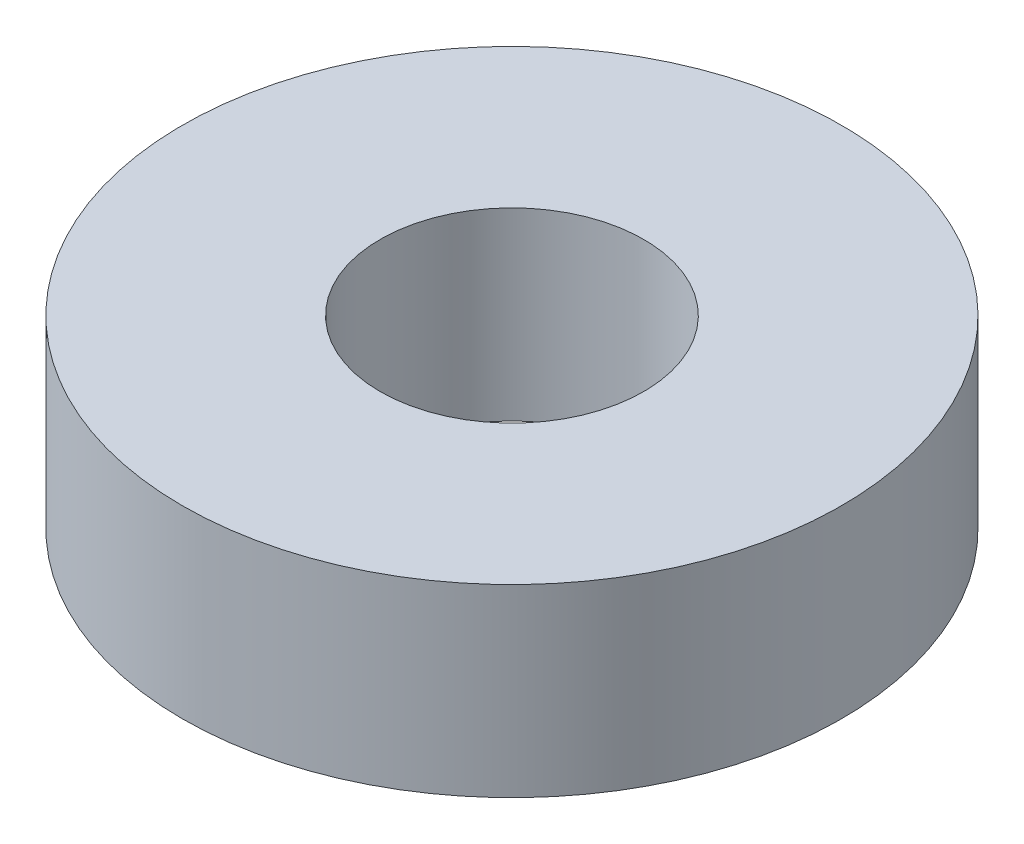
SolidWorks part; units mm, degrees
ref_plane "Front Plane" through (0, 0, 0) normal (0, 0, 1) x (1, 0, 0)
ref_plane "Top Plane" through (0, 0, 0) normal (0, 1, 0) x (1, 0, 0)
ref_plane "Right Plane" through (0, 0, 0) normal (1, 0, 0) x (0, 0, -1)
sketch "Sketch1" plane through (0, 0, 0) normal (0, 1, 0) x (1, 0, 0)
  circle A0 centre (0, 0) radius 50
  dimension "FLANGE_OD" = 100
extrude "Boss-Extrude1" add sketch "Sketch1" along normal blind 28
sketch "Sketch2" plane through (0, 0, 0) normal (0, 1, 0) x (1, 0, 0)
  circle A0 centre (0, 0) radius 20
  dimension "BORE_D" = 40
extrude "Cut-Extrude1" cut sketch "Sketch2" along normal through all
sketch "Sketch3" plane through (0, 28, 0) normal (0, 1, 0) x (1, 0, 0)
  circle A0 centre (0, 0) radius 16.0016 construction
  circle A1 centre (-16.0016, 0) radius 2.1528
  dimension "BOLT_D" = 4.3057
  dimension "BOLT_PCD" = 32.0031
extrude "Cut-Extrude2" cut sketch "Sketch3" against normal blind 22.9969 rebuild error yes
pattern_circular "CirPattern1" count 8 over 360 rebuild error yes
